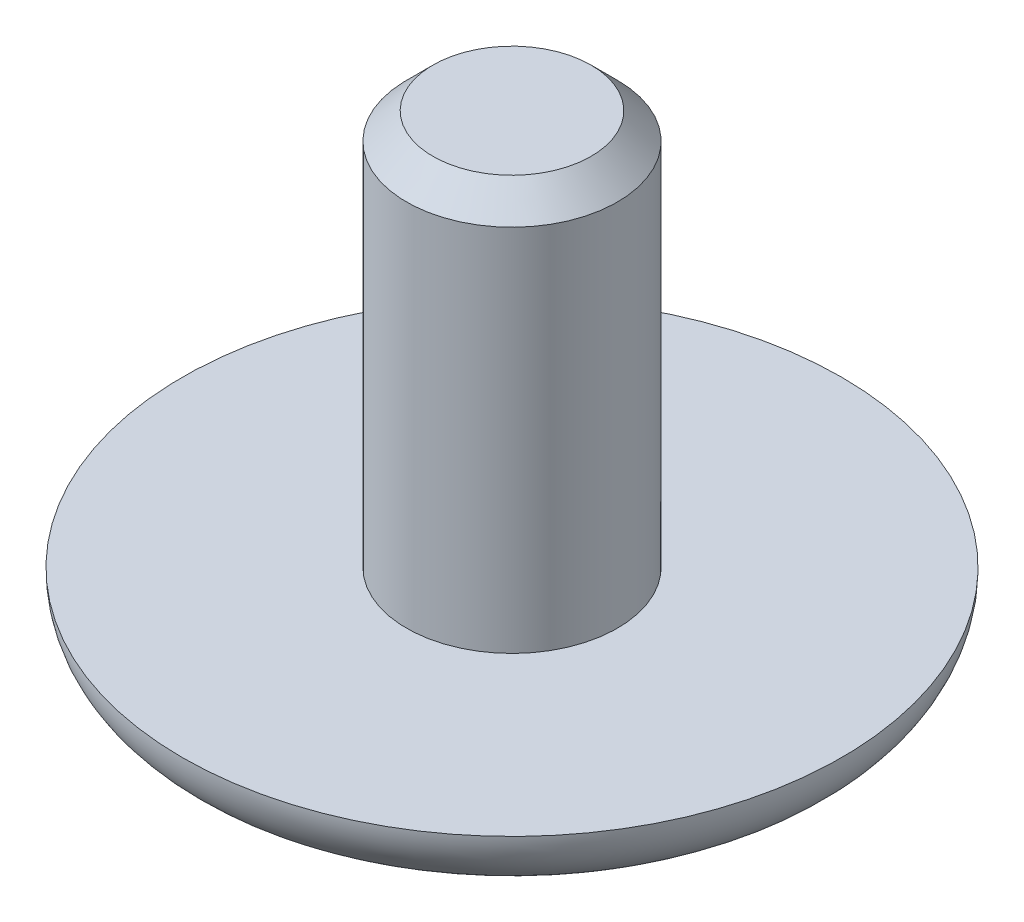
SolidWorks part; units mm, degrees
material "AISI 321 退火不锈钢 (SS)"
ref_plane "前视基准面" through (0, 0, 0) normal (0, 0, 1) x (1, 0, 0)
ref_plane "上视基准面" through (0, 0, 0) normal (0, 1, 0) x (1, 0, 0)
ref_plane "右视基准面" through (0, 0, 0) normal (1, 0, 0) x (0, 0, -1)
other "Configuration Table"
sketch "草图1" plane through (0, 0, 0) normal (0, 0, 1) x (1, 0, 0)
  line L0 (0, 0) -> (-2.5, 0)
  line L1 (-2.5, 0) -> (-2.5, 0.5)
  line L2 (-2.5, 0.5) -> (-0.8, 0.5)
  line L3 (-0.8, 0.5) -> (-0.8, 3.5)
  line L4 (-0.8, 3.5) -> (0, 3.5)
  line L5 (0, 3.5) -> (0, 0)
  line L6 (0, 0) -> (0, 6.259) construction
  dimension "D1" = 1.6
  dimension "D2" = 3
  dimension "D3" = 5
  dimension "D4" = 0.5
revolve "旋转1" add sketch "草图1" angle 360 about L6
cosmetic thread "装饰螺纹线1" parameters "D2"=1.221
chamfer "倒角1" distance 0.2 angle 45 1 edges at (0, 3.5, -0.8)
fillet "圆角1" radius 0.5 1 edges at (0, 0, -2.5)
sketch "草图2" plane through (0, 0, 0) normal (0, -1, 0) x (1, 0, 0)
  line L1 (-0.4, 1.75) -> (0.4, 1.75)
  line L2 (-0.4, 1.75) -> (-0.4, -1.75)
  line L3 (-0.4, -1.75) -> (0.4, -1.75)
  line L4 (0.4, 1.75) -> (0.4, -1.75)
  line L5 (-0.4, 1.75) -> (0.4, -1.75) construction
  line L6 (-0.4, -1.75) -> (0.4, 1.75) construction
  line L7 (-1.75, 0.4) -> (1.75, 0.4)
  line L8 (-1.75, 0.4) -> (-1.75, -0.4)
  line L9 (-1.75, -0.4) -> (1.75, -0.4)
  line L10 (1.75, 0.4) -> (1.75, -0.4)
  line L11 (-1.75, 0.4) -> (1.75, -0.4) construction
  line L12 (-1.75, -0.4) -> (1.75, 0.4) construction
  point P0 (0, 0)
  point P6 (0, 0)
  dimension "D1" = 0.8
  dimension "D2" = 0.8
  dimension "D3" = 3.5
  dimension "D4" = 3.5
extrude "切除-拉伸1" cut sketch "草图2" against normal blind 0.3 draft 25 contours L10 L7 L4 L9 | L2 L9 L4 L7 | L9 L2 L3 L4 | L8 L9 L2 L7 | L2 L7 L4 L1 region at (0, 0, 1.075) region at (0, 0, 0) region at (-1.075, 0, 0) region at (1.075, 0, 0) region at (0, 0, -1.075)
